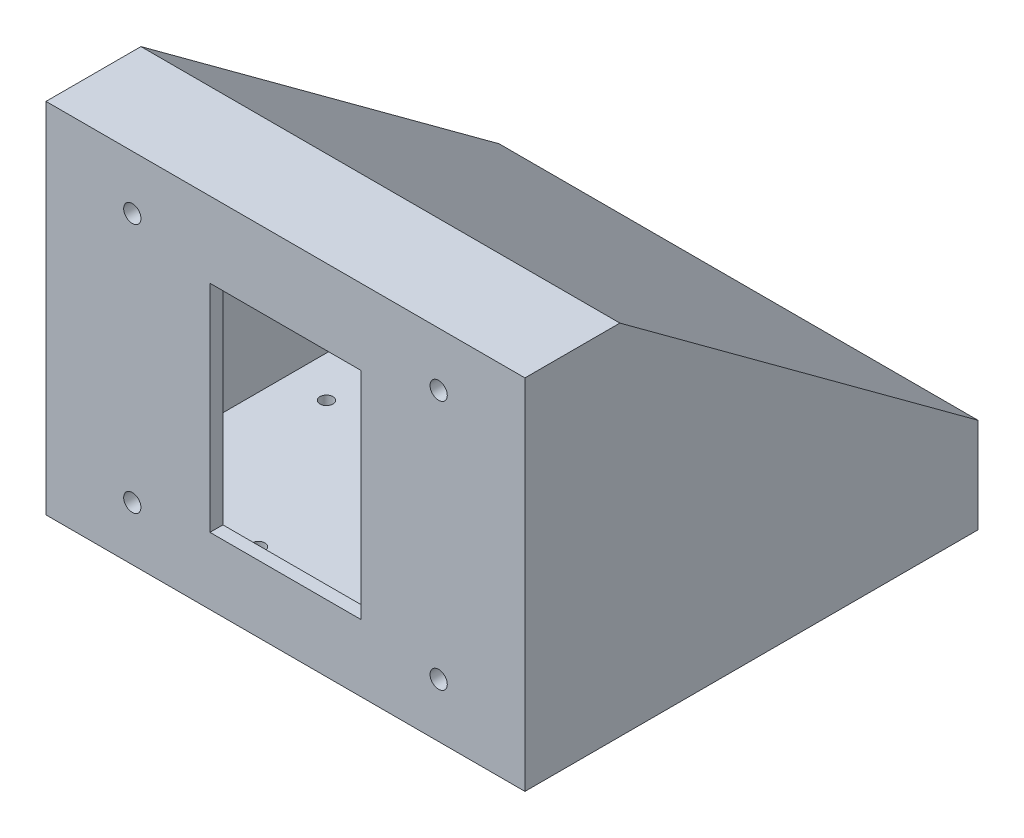
SolidWorks part; units mm, degrees
ref_plane "Front Plane" through (0, 0, 0) normal (0, 0, 1) x (1, 0, 0)
ref_plane "Top Plane" through (0, 0, 0) normal (0, 1, 0) x (1, 0, 0)
ref_plane "Right Plane" through (0, 0, 0) normal (1, 0, 0) x (0, 0, -1)
sketch "Sketch1" plane through (0, 0, 0) normal (0, 1, 0) x (1, 0, 0)
  line L1 (0, 0) -> (210, 0)
  line L2 (0, 0) -> (0, 210)
  line L3 (0, 210) -> (210, 210)
  line L4 (210, 0) -> (210, 210)
  circle A0 centre (105, 105) radius 100 construction
  circle A1 centre (62, 179.4782) radius 3
  circle A2 centre (148, 179.4782) radius 3
  circle A3 centre (191, 105) radius 3
  circle A4 centre (148, 30.5218) radius 3
  circle A5 centre (62, 30.5218) radius 3
  circle A6 centre (19, 105) radius 3
  point P10 (105, 105)
  point P11 (61.8577, 179.3959)
  point P21 (105, 105)
  point P22 (0, 0)
  dimension "D1" = 200
  dimension "D6" = 6
  dimension "D2" = 210
  dimension "D3" = 105
  dimension "D4" = 210
  dimension "D5" = 105
  dimension "D8" = 86
  dimension "D7" = 6
extrude "Boss-Extrude1" add sketch "Sketch1" along normal blind 6
sketch "Sketch3" plane through (0, 6, 0) normal (0, 1, 0) x (1, 0, 0)
  line L0 (210, 0) -> (210, 210) construction
  line L1 (0, 0) -> (210, 0)
  line L2 (0, 0) -> (0, 6)
  line L3 (0, 6) -> (210, 6)
  line L4 (210, 0) -> (210, 6)
  dimension "D1" = 6
extrude "Boss-Extrude2" add sketch "Sketch3" along normal blind 160
sketch "Sketch4" plane through (0, 0, 0) normal (-1, 0, 0) x (0, 0, 1)
  line L0 (0, 0) -> (-210, 0)
  line L1 (-210, 0) -> (-210, 44)
  line L2 (-210, 44) -> (-44, 166)
  line L3 (-44, 166) -> (0, 166)
  line L4 (0, 166) -> (0, 0)
  dimension "D1" = 44
  dimension "D2" = 44
extrude "Boss-Extrude4" add sketch "Sketch4" along normal blind 6
extrude "Boss-Extrude5" add sketch "Sketch4<3>" against normal blind 6 from offset 210 offset against normal yes
sketch "Sketch4<3>" plane through (0, 0, 0) normal (-1, 0, 0) x (0, 0, 1) same geometry as "Sketch4"
sketch "Sketch6" plane through (0, 0, -6) normal (0, 0, -1) x (-1, 0, 0)
  line L4 (-70, 131) -> (-70, 31)
  line L5 (-140, 131) -> (-70, 131)
  line L6 (-140, 131) -> (-140, 31)
  line L7 (-140, 31) -> (-70, 31)
  line L9 (-150, 166) -> (-150, 6) construction
  line L10 (-210, 166) -> (0, 166) construction
  line L11 (-210, 6) -> (0, 6) construction
  line L12 (-60, 166) -> (-60, 6) construction
  line L13 (-210, 166) -> (-210, 6) construction
  point P0 (-104.0516, 30.4965)
  point P22 (0, 0)
  dimension "D1" = 70
  dimension "D2" = 100
  dimension "D3" = 90
  dimension "D4" = 60
  dimension "D5" = 70
  dimension "D6" = 25
extrude "Cut-Extrude1" cut sketch "Sketch6" against normal through all
sketch "Sketch7" plane through (0, 0, -210) normal (0, 0, -1) x (-1, 0, 0)
  line L1 (0, 6) -> (-210, 6)
  line L2 (0, 6) -> (0, 44)
  line L3 (0, 44) -> (-210, 44)
  line L4 (-210, 6) -> (-210, 44)
extrude "Boss-Extrude6" add sketch "Sketch7" against normal blind 6
sketch "Sketch8" plane through (0, 128.7791, -94.6449) normal (0, 0.8058, -0.5922) x (1, 0, 0)
  line L1 (-6, 143.1583) -> (216, 143.1583)
  line L2 (-6, 143.1583) -> (-6, -62.8514)
  line L3 (-6, -62.8514) -> (216, -62.8514)
  line L4 (216, 143.1583) -> (216, -62.8514)
extrude "Boss-Extrude7" add sketch "Sketch8" against normal blind 6
sketch "Sketch9" plane through (0, 166, 0) normal (0, 1, 0) x (1, 0, 0)
  line L1 (216, 0) -> (-6, 0)
  line L2 (216, 0) -> (216, 44)
  line L3 (216, 44) -> (-6, 44)
  line L4 (-6, 0) -> (-6, 44)
extrude "Boss-Extrude8" add sketch "Sketch9" against normal blind 6
sketch "Sketch10" plane through (0, 0, 0) normal (0, 0, 1) x (1, 0, 0)
  line L0 (-6, 0) -> (-6, 166) construction
  line L1 (-6, 0) -> (216, 0) construction
  line L2 (-6, 166) -> (216, 166) construction
  line L3 (216, 0) -> (216, 166) construction
  line L4 (60, 166) -> (60, 0) construction
  line L5 (150, 166) -> (150, 0) construction
  circle A0 centre (176, 141) radius 4
  circle A1 centre (34, 141) radius 4
  circle A2 centre (34, 25) radius 4
  circle A3 centre (176, 25) radius 4
  dimension "D1" = 8
  dimension "D2" = 25
  dimension "D3" = 25
  dimension "D4" = 40
  dimension "D5" = 90
  dimension "D6" = 66
  dimension "D7" = 40
extrude "Cut-Extrude2" cut sketch "Sketch10" against normal up to next
